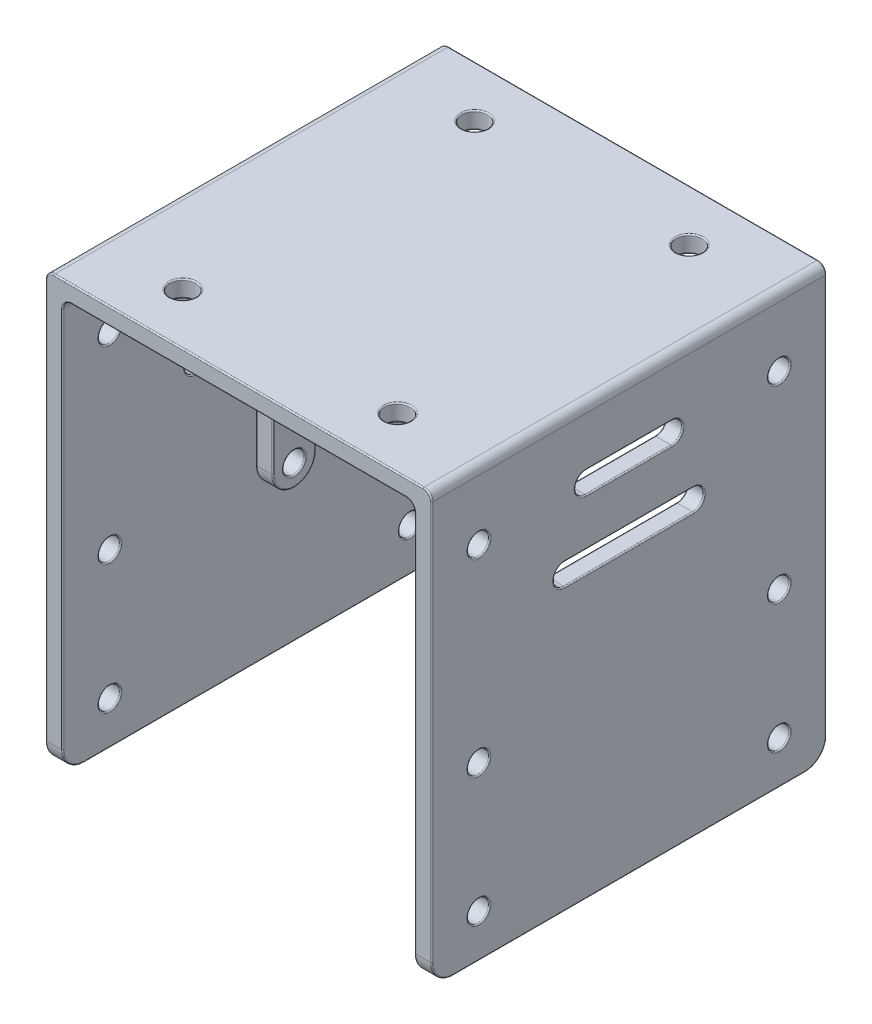
SolidWorks part; units mm, degrees
ref_plane "Front Plane" through (0, 0, 0) normal (0, 0, 1) x (1, 0, 0)
ref_plane "Top Plane" through (0, 0, 0) normal (0, 1, 0) x (1, 0, 0)
ref_plane "Right Plane" through (0, 0, 0) normal (1, 0, 0) x (0, 0, -1)
sketch "Sketch1" plane through (0, 0, 0) normal (0, 0, 1) x (1, 0, 0)
  line L0 (-22.5, -50) -> (-22.5, 0)
  line L1 (-22.5, 0) -> (22.5, 0)
  line L2 (22.5, 0) -> (22.5, -50)
  line L3 (-20.5, -50) -> (-20.5, -2)
  line L4 (-20.5, -2) -> (20.5, -2)
  line L5 (20.5, -2) -> (20.5, -50)
  line L6 (-22.5, -50) -> (-20.5, -50)
  line L8 (20.5, -50) -> (22.5, -50)
  point P2 (0, 0)
  dimension "D1" = 45
  dimension "D2" = 50
  dimension "D3" = 2
extrude "Boss-Extrude1" add sketch "Sketch1" along normal blind 23 and the other way blind 23
sketch "Sketch2" plane through (0, 0, 0) normal (0, 1, 0) x (1, 0, 0)
  line L0 (0, 0) -> (0, 11.7657) construction
  line L1 (0, 0) -> (-12.4746, 0) construction
  circle A0 centre (-12.5, 17) radius 1.5
  circle A1 centre (12.5, 17) radius 1.5
  circle A2 centre (12.5, -17) radius 1.5
  circle A3 centre (-12.5, -17) radius 1.5
  point P8 (0, 0)
  dimension "D1" = 3
  dimension "D2" = 25
  dimension "D3" = 17
extrude "Cut-Extrude1" cut sketch "Sketch2" against normal up to surface (2 mm away) up to face at (0, -2, 0)
sketch "Sketch3" plane through (0, 0, 0) normal (1, 0, 0) x (0, 0, -1)
  line L0 (0, 0) -> (0, -26.4789) construction
  line L1 (23, 0) -> (-23, 0) construction
  circle A0 centre (-17.5, -8) radius 1.25
  circle A1 centre (-17.5, -30) radius 1.25
  circle A2 centre (-17.5, -45) radius 1.25
  circle A3 centre (17.5, -45) radius 1.25
  circle A4 centre (17.5, -30) radius 1.25
  circle A5 centre (17.5, -8) radius 1.25
  dimension "D1" = 2.5
  dimension "D2" = 8
  dimension "D3" = 30
  dimension "D4" = 15
  dimension "D5" = 17.5
extrude "Cut-Extrude2" cut sketch "Sketch3" against normal up to surface and the other way up to surface up to face at (-22.5, -25, 0) other way up to face at (22.5, -25, 0)
sketch "Sketch4" plane through (0, 0, 0) normal (1, 0, 0) x (0, 0, -1)
  line L0 (-5, -8) -> (5, -8) construction
  line L1 (-5, -6.75) -> (5, -6.75)
  line L2 (-5, -9.25) -> (5, -9.25)
  line L3 (-7.5, -16) -> (7.5, -16) construction
  line L4 (-7.5, -14.75) -> (7.5, -14.75)
  line L5 (-7.5, -17.25) -> (7.5, -17.25)
  line L6 (23, 0) -> (-23, 0) construction
  arc A0 (-5, -6.75) -> (-5, -9.25) centre (-5, -8) ccw
  arc A1 (5, -9.25) -> (5, -6.75) centre (5, -8) ccw
  arc A2 (-7.5, -14.75) -> (-7.5, -17.25) centre (-7.5, -16) ccw
  arc A3 (7.5, -17.25) -> (7.5, -14.75) centre (7.5, -16) ccw
  point P2 (0, -8)
  point P7 (0, -16)
  point P14 (0, 0)
  dimension "D1" = 8
  dimension "D2" = 8
  dimension "D3" = 10
  dimension "D4" = 2.5
  dimension "D5" = 2.5
  dimension "D6" = 15
extrude "Cut-Extrude3" cut sketch "Sketch4" against normal up to surface and the other way up to surface up to face at (-22.5, -8, -16.25) other way up to face at (22.5, -6.75, -17.5)
fillet "Fillet1" radius 2.5 4 edges at (21.5, -50, -23) (21.5, -50, 23) (-21.5, -50, -23) (-21.5, -50, 23)
fillet "Fillet2" radius 1 4 edges at (-20.5, -2, 0) (20.5, -2, 0) (-22.5, 0, 0) (22.5, 0, 0)
sketch "Sketch5" plane through (0, 0, 0) normal (1, 0, 0) x (0, 0, -1)
  line L0 (0, 0) -> (0, -31.6795) construction
  line L1 (-23, -3) -> (23, -3) construction
  line L2 (-15, -10.5) -> (-15, -2)
  line L3 (-20, -10.5) -> (-20, -2)
  line L4 (-20, -2) -> (-15, -2)
  line L5 (23, -2) -> (-23, -2) construction
  line L6 (20, -2) -> (15, -2)
  line L7 (20, -10.5) -> (20, -2)
  line L8 (15, -10.5) -> (15, -2)
  circle A0 centre (-17.5, -10.5) radius 1.25
  arc A1 (-20, -10.5) -> (-15, -10.5) centre (-17.5, -10.5) ccw
  circle A2 centre (-17.5, -10.5) radius 2.5 construction
  arc A3 (20, -10.5) -> (15, -10.5) centre (17.5, -10.5) cw
  circle A4 centre (17.5, -10.5) radius 1.25
  dimension "D1" = 2.5
  dimension "D2" = 17.5
  dimension "D3" = 7.5
  dimension "D4" = 1.25
extrude "Boss-Extrude2" add sketch "Sketch5" along normal blind 1 and the other way blind 1
fillet "Fillet3" radius 0.15 120 edges at (1, -10.5, -16.25) (1, -13, -17.5) (1, -6.25, -20) (1, -2, -17.5) (1, -6.25, -15) (-1, -10.5, -16.25) (-1, -13, -17.5) (-1, -6.25, -20) (-1, -2, -17.5) (-1, -6.25, -15) (0, -2, -20) (0, -2, -15) (1, -10.5, 16.25) (1, -13, 17.5) (1, -6.25, 15) (1, -2, 17.5) (1, -6.25, 20) (-1, -10.5, 16.25) (-1, -13, 17.5) (-1, -6.25, 15) (-1, -2, 17.5) (-1, -6.25, 20) (0, -2, 15) (0, -2, 20) (22.5, -14.75, 0) (22.5, -16, 8.75) (22.5, -17.25, 0) (22.5, -16, -8.75) (-22.5, -17.25, 0) (-22.5, -16, -8.75) (-22.5, -14.75, 0) (-22.5, -16, 8.75) (22.5, -6.75, 0) (22.5, -8, 6.25) (22.5, -9.25, 0) (22.5, -8, -6.25) (-22.5, -9.25, 0) (-22.5, -8, -6.25) (-22.5, -6.75, 0) (-22.5, -8, 6.25) (20.5, -16, 8.75) (20.5, -14.75, 0) (20.5, -16, -8.75) (20.5, -17.25, 0) (20.5, -8, 6.25) (20.5, -6.75, 0) (20.5, -8, -6.25) (20.5, -9.25, 0) (22.5, -6.75, -17.5) (-22.5, -8, -16.25) (22.5, -28.75, -17.5) (-22.5, -30, -16.25) (22.5, -43.75, -17.5) (-22.5, -45, -16.25) (22.5, -43.75, 17.5) (-22.5, -45, 18.75) (22.5, -28.75, 17.5) (-22.5, -30, 18.75) (22.5, -6.75, 17.5) (-22.5, -8, 18.75) (-20.5, -8, 16.25) (20.5, -8, 18.75) (-20.5, -30, 16.25) (20.5, -30, 18.75) (-20.5, -45, 16.25) (20.5, -45, 18.75) (-20.5, -45, -18.75) (20.5, -45, -16.25) (-20.5, -30, -18.75) (20.5, -30, -16.25) (-20.5, -8, -18.75) (20.5, -8, -16.25) (-11, 0, 17) (-12.5, -2, 15.5) (14, 0, 17) (12.5, -2, 15.5) (11, 0, -17) (12.5, -2, -18.5) (-14, 0, -17) (-12.5, -2, -18.5) (-20.5, -25.25, 23) (0, -2, 23) (20.5, -25.25, 23) (22.5, -24.25, 23) (0, 0, 23) (-22.5, -24.25, 23) (0, -2, -23) (20.5, -25.25, -23) (22.5, -24.25, -23) (0, 0, -23) (-22.5, -24.25, -23) (-20.5, -50, 0) (20.5, -50, 0) (22.5, -50, 0) (-22.5, -50, 0) (-20.5, -16, 8.75) (-20.5, -14.75, 0) (-20.5, -16, -8.75) (-20.5, -17.25, 0) (-20.5, -8, 6.25) (-20.5, -6.75, 0) (-20.5, -8, -6.25) (-20.5, -9.25, 0) (22.5, -49.2678, 22.2678) (22.5, -49.2678, -22.2678) (20.5, -49.2678, 22.2678) (20.5, -49.2678, -22.2678) (-20.5, -49.2678, 22.2678) (-20.5, -49.2678, -22.2678) (-22.5, -49.2678, 22.2678) (-22.5, -49.2678, -22.2678) (22.2071, -0.2929, 23) (-22.2071, -0.2929, 23) (22.2071, -0.2929, -23) (-22.2071, -0.2929, -23) (-20.2071, -2.2929, 23) (-20.2071, -2.2929, -23) (20.2071, -2.2929, 23) (20.2071, -2.2929, -23) (-20.5, -25.25, -23)
